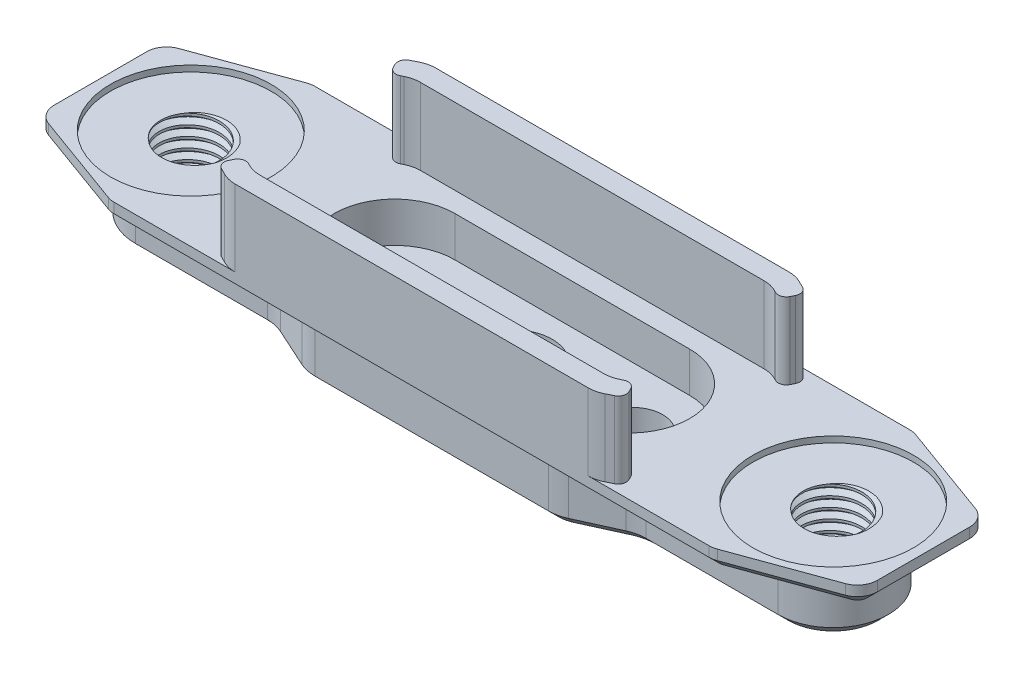
SolidWorks part; units mm, degrees
material "6061-T6 (SS)"
ref_plane "Front Plane" through (0, 0, 0) normal (0, 0, 1) x (1, 0, 0)
ref_plane "Top Plane" through (0, 0, 0) normal (0, 1, 0) x (1, 0, 0)
ref_plane "Right Plane" through (0, 0, 0) normal (1, 0, 0) x (0, 0, -1)
sketch "Sketch1" plane through (0, 0, 0) normal (0, 1, 0) x (1, 0, 0)
  line L1 (14.8238, -5) -> (-14.8238, -5)
  line L2 (20.5, -2.2996) -> (20.5, 2.2996)
  line L3 (14.8238, 5) -> (-14.8238, 5)
  line L4 (-20.5, -2.2996) -> (-20.5, 2.2996)
  line L5 (17.208, -4.1971) -> (-17.208, 4.1971) construction
  line L6 (17.208, 4.1971) -> (-17.208, -4.1971) construction
  line L9 (15.1656, 4.9398) -> (19.8417, 3.2394)
  line L11 (19.8417, -3.2394) -> (15.1656, -4.9398)
  line L12 (0, 7.9885) -> (0, -7.9189) construction
  line L13 (-19.8417, -3.2394) -> (-15.1656, -4.9398)
  line L14 (-15.1656, 4.9398) -> (-19.8417, 3.2394)
  arc A0 (-19.8417, 3.2394) -> (-20.5, 2.2996) centre (-19.5, 2.2996) ccw
  arc A1 (-19.8417, -3.2394) -> (-20.5, -2.2996) centre (-19.5, -2.2996) cw
  arc A2 (19.8417, -3.2394) -> (20.5, -2.2996) centre (19.5, -2.2996) ccw
  arc A3 (19.8417, 3.2394) -> (20.5, 2.2996) centre (19.5, 2.2996) cw
  arc A4 (-15.1656, 4.9398) -> (-14.8238, 5) centre (-14.8238, 4) cw
  arc A5 (-15.1656, -4.9398) -> (-14.8238, -5) centre (-14.8238, -4) ccw
  arc A6 (15.1656, -4.9398) -> (14.8238, -5) centre (14.8238, -4) cw
  arc A7 (15.1656, 4.9398) -> (14.8238, 5) centre (14.8238, 4) ccw
  point P0 (0, 0)
  point P8 (-20.5, 3)
  point P12 (-20.5, -3)
  point P24 (20.5, -3)
  point P27 (20.5, 3)
  point P30 (-15, 5)
  point P33 (-15, -5)
  point P36 (15, -5)
  point P39 (15, 5)
  dimension "D1" = 1
  dimension "D2" = 10
  dimension "D3" = 30
  dimension "D4" = 15
  dimension "D5" = 6
  dimension "D6" = 3
extrude "Boss-Extrude1" add sketch "Sketch1" along normal blind 1
chamfer "Chamfer1" distance 0.5 angle 45 16 edges at (0, 0, -5) (-14.9973, 0, -4.9848) (14.9973, 0, -4.9848) (-17.5037, 0, -4.0896) (17.5037, 0, -4.0896) (-20.3191, 0, -2.8733) (20.3191, 0, -2.8733) (-20.5, 0, 0) (20.5, 0, 0) (-20.3191, 0, 2.8733) (20.3191, 0, 2.8733) (-17.5037, 0, 4.0896) (17.5037, 0, 4.0896) (-14.9973, 0, 4.9848) (14.9973, 0, 4.9848) (0, 0, 5)
sketch "Sketch2" plane through (0, 0, 0) normal (0, -1, 0) x (1, 0, 0)
  line L0 (-16, 2.75) -> (-9.4332, 2.75)
  line L1 (5.8168, -4) -> (-5.8168, -4)
  line L3 (5.8168, 4) -> (-5.8168, 4)
  line L5 (9.4332, 2.75) -> (16, 2.75)
  line L7 (-16, -2.75) -> (-9.4332, -2.75)
  line L8 (-9, 0) -> (8.1313, 0) construction
  line L9 (6.6444, -3.8207) -> (8.6056, -2.9293)
  line L10 (-8.6056, -2.9293) -> (-6.6444, -3.8207)
  line L11 (-8.6056, 2.9293) -> (-6.6444, 3.8207)
  line L12 (9.4332, -2.75) -> (16, -2.75)
  line L13 (6.6444, 3.8207) -> (8.6056, 2.9293)
  arc A0 (8.6056, 2.9293) -> (9.4332, 2.75) centre (9.4332, 4.75) ccw
  arc A1 (6.6444, 3.8207) -> (5.8168, 4) centre (5.8168, 2) ccw
  arc A2 (-6.6444, 3.8207) -> (-5.8168, 4) centre (-5.8168, 2) cw
  arc A3 (-8.6056, 2.9293) -> (-9.4332, 2.75) centre (-9.4332, 4.75) cw
  arc A4 (-6.6444, -3.8207) -> (-5.8168, -4) centre (-5.8168, -2) ccw
  arc A5 (-8.6056, -2.9293) -> (-9.4332, -2.75) centre (-9.4332, -4.75) ccw
  arc A6 (8.6056, -2.9293) -> (9.4332, -2.75) centre (9.4332, -4.75) cw
  arc A7 (6.6444, -3.8207) -> (5.8168, -4) centre (5.8168, -2) cw
  circle A11 centre (0, 0) radius 2
  circle A12 centre (-6, 0) radius 1.5
  circle A13 centre (6, 0) radius 1.5
  arc A14 (-16, 2.75) -> (-16, -2.75) centre (-16, 0) ccw
  arc A15 (16, -2.75) -> (16, 2.75) centre (16, 0) ccw
  point P0 (0, 0)
  point P9 (-18.75, 0)
  point P16 (9, 2.75)
  point P23 (6.25, 4)
  point P26 (-6.25, 4)
  point P29 (-9, 2.75)
  point P32 (-6.25, -4)
  point P35 (-9, -2.75)
  point P38 (9, -2.75)
  point P41 (6.25, -4)
  point P50 (18.75, 0)
  dimension "D12" = 2
  dimension "D17" = 4
  dimension "D20" = 3
  dimension "D21" = 3
  dimension "D22" = 18.75
  dimension "D2" = 8
  dimension "D3" = 5.5
  dimension "D4" = 5.5
  dimension "D5" = 18
  dimension "D6" = 9
  dimension "D7" = 12.5
  dimension "D8" = 6.25
  dimension "D9" = 37.5
  dimension "D10" = 2.75
  dimension "D11" = 4
  dimension "D13" = 32
  dimension "D14" = 16
  dimension "D18" = 12
  dimension "D19" = 6
extrude "Boss-Extrude2" add sketch "Sketch2" along normal blind 3
chamfer "Chamfer2" distance 0.5 angle 45 20 edges at (12.7166, -3, 2.75) (9.0098, -3, 2.7953) (18.75, -3, 0) (7.625, -3, 3.375) (12.7166, -3, -2.75) (6.2402, -3, 3.9547) (9.0098, -3, -2.7953) (0, -3, 4) (7.625, -3, -3.375) (-6.2402, -3, 3.9547) (6.2402, -3, -3.9547) (-7.625, -3, 3.375) (0, -3, -4) (-9.0098, -3, 2.7953) (-6.2402, -3, -3.9547) (-12.7166, -3, 2.75) (-7.625, -3, -3.375) (-18.75, -3, 0) (-9.0098, -3, -2.7953) (-12.7166, -3, -2.75)
sketch "Sketch4" plane through (0, 1, 0) normal (0, 1, 0) x (1, 0, 0)
  circle A2 centre (-16, 0) radius 4
  circle A3 centre (16, 0) radius 4
  dimension "D1" = 32
  dimension "D2" = 16
  dimension "D3" = 8
  dimension "D4" = 8
extrude "Cut-Extrude2" cut sketch "Sketch4" against normal blind 0.3
sketch "Sketch5" plane through (0, 1, 0) normal (0, 1, 0) x (1, 0, 0)
  line L1 (5.85, -3) -> (-5.85, -3)
  line L3 (5.85, 3) -> (-5.85, 3)
  arc A0 (-5.85, 3) -> (-5.85, -3) centre (-5.85, 0) ccw
  arc A1 (5.85, -3) -> (5.85, 3) centre (5.85, 0) ccw
  point P0 (0, 0)
  point P1 (-8.85, 0)
  point P2 (8.85, 0)
  dimension "D3" = 8.85
  dimension "D1" = 17.7
  dimension "D2" = 6
extrude "Cut-Extrude3" cut sketch "Sketch5" against normal blind 2
sketch "Sketch6" plane through (0, 1, 0) normal (0, 1, 0) x (1, 0, 0)
  line L0 (-10.15, 7.0956) -> (-10.15, 1.2772) construction
  line L1 (-11.7314, 4.5) -> (12.299, 4.5) construction
  line L2 (10.15, 7.0956) -> (10.15, 2.7909) construction
  line L3 (14.8238, 5) -> (-14.8238, 5) construction
  line L4 (-9.15, 5.9263) -> (-9.15, 4.063) construction
  line L5 (-8.7959, 5) -> (8.7959, 5)
  line L6 (9.15, 5.9263) -> (9.15, 4.5569) construction
  line L7 (0, 0) -> (0, 2.7909) construction
  line L8 (-9.4667, 4.8416) -> (-9.7922, 4.6789)
  line L9 (9.4667, 4.8416) -> (9.7922, 4.6789)
  line L10 (9.2307, 3.8416) -> (9.345, 3.7845)
  line L11 (-8.5598, 4) -> (8.5598, 4)
  line L12 (-9.2307, 3.8416) -> (-9.345, 3.7845)
  line L13 (-9.9711, 4.1422) -> (-9.8817, 3.9633)
  line L14 (9.9711, 4.1422) -> (9.8817, 3.9633)
  line L15 (8.9139, 4) -> (9.7028, 3.6056) construction
  line L16 (-8.9139, 4) -> (8.9139, 4) construction
  line L17 (9.15, 5) -> (10.15, 4.5) construction
  line L18 (-9.15, 5) -> (9.15, 5) construction
  line L19 (-8.9139, 4) -> (-9.7028, 3.6056) construction
  line L20 (-9.15, 5) -> (-10.15, 4.5) construction
  line L21 (-6, 0) -> (6.1193, 0) construction
  line L22 (9.15, -5.9263) -> (9.15, -4.5569) construction
  line L23 (-9.15, -5.9263) -> (-9.15, -4.063) construction
  line L24 (-11.7314, -4.5) -> (12.299, -4.5) construction
  line L25 (9.9711, -4.1422) -> (9.8817, -3.9633)
  line L26 (-9.9711, -4.1422) -> (-9.8817, -3.9633)
  line L27 (-9.2307, -3.8416) -> (-9.345, -3.7845)
  line L28 (-8.5598, -4) -> (8.5598, -4)
  line L29 (9.2307, -3.8416) -> (9.345, -3.7845)
  line L30 (9.4667, -4.8416) -> (9.7922, -4.6789)
  line L31 (-9.4667, -4.8416) -> (-9.7922, -4.6789)
  line L32 (-8.7959, -5) -> (8.7959, -5)
  arc A1 (9.2307, 3.8416) -> (8.5598, 4) centre (8.5598, 2.5) ccw
  arc A2 (9.4667, 4.8416) -> (8.7959, 5) centre (8.7959, 3.5) ccw
  arc A4 (-8.5598, 4) -> (-9.2307, 3.8416) centre (-8.5598, 2.5) ccw
  arc A5 (-8.7959, 5) -> (-9.4667, 4.8416) centre (-8.7959, 3.5) ccw
  arc A6 (-9.8817, 3.9633) -> (-9.345, 3.7845) centre (-9.5239, 4.1422) ccw
  arc A7 (-9.9711, 4.1422) -> (-9.7922, 4.6789) centre (-9.6133, 4.3211) cw
  arc A8 (9.345, 3.7845) -> (9.8817, 3.9633) centre (9.5239, 4.1422) ccw
  arc A9 (9.9711, 4.1422) -> (9.7922, 4.6789) centre (9.6133, 4.3211) ccw
  arc A10 (9.9711, -4.1422) -> (9.7922, -4.6789) centre (9.6133, -4.3211) cw
  arc A11 (9.345, -3.7845) -> (9.8817, -3.9633) centre (9.5239, -4.1422) cw
  arc A12 (-9.9711, -4.1422) -> (-9.7922, -4.6789) centre (-9.6133, -4.3211) ccw
  arc A13 (-9.8817, -3.9633) -> (-9.345, -3.7845) centre (-9.5239, -4.1422) cw
  arc A14 (-8.7959, -5) -> (-9.4667, -4.8416) centre (-8.7959, -3.5) cw
  arc A15 (-8.5598, -4) -> (-9.2307, -3.8416) centre (-8.5598, -2.5) cw
  arc A16 (9.4667, -4.8416) -> (8.7959, -5) centre (8.7959, -3.5) cw
  arc A17 (9.2307, -3.8416) -> (8.5598, -4) centre (8.5598, -2.5) cw
  point P29 (9.15, 5)
  point P81 (9.15, -5)
  dimension "D6" = 1.5
  dimension "D7" = 0.4
  dimension "D1" = 20.3
  dimension "D2" = 10.15
  dimension "D3" = 0.5
  dimension "D4" = 1
  dimension "D5" = 9.15
extrude "Boss-Extrude3" add sketch "Sketch6" along normal blind 3.8
sketch "Sketch10" plane through (0, 0.7, 0) normal (0, 1, 0) x (1, 0, 0)
  circle A0 centre (-16, 0) radius 1.5
  circle A1 centre (16, 0) radius 1.5
  dimension "D1" = 3
  dimension "D2" = 3
extrude "Cut-Extrude4" cut sketch "Sketch10" against normal through all
thread "Thread4" pitch 0.5 method cut profile "Thread Profile5" start angle 0, offset 0, length 0, pitch 0.5, diameter 3
ref_plane "Plane5" through (-14.5, -3, 0) normal (0, 0, 1) x (1, 0, 0)
sketch "Thread Profile5" plane through (-14.5, -3, 0) normal (0, 0, 1) x (1, 0, 0)
  line L0 (0, 0) -> (0, 0.5) construction
  line L1 (0, 0) -> (0.2706, 0.1562)
  line L2 (0.2706, 0.1562) -> (0.2706, 0.2187)
  line L3 (0.2706, 0.2187) -> (0, 0.375)
  line L4 (0.2706, 0.1875) -> (0, 0.1875) construction
  line L11 (0, 0) -> (0, 0.375)
  point P2 (0, 0)
  dimension "Pitch" = 0.5
  dimension "Profile_Angle" = 60
  dimension "Profile_Land" = 0.0625
  dimension "Profile_Height" = 0.2706
thread "Thread5" pitch 0.5 method cut profile "Thread Profile6" start angle 0, offset 0, length 0, pitch 0.5, diameter 3
ref_plane "Plane6" through (17.5, -3, 0) normal (0, 0, 1) x (1, 0, 0)
sketch "Thread Profile6" plane through (17.5, -3, 0) normal (0, 0, 1) x (1, 0, 0)
  line L0 (0, 0) -> (0, 0.5) construction
  line L1 (0, 0) -> (0.2706, 0.1562)
  line L2 (0.2706, 0.1562) -> (0.2706, 0.2187)
  line L3 (0.2706, 0.2187) -> (0, 0.375)
  line L4 (0.2706, 0.1875) -> (0, 0.1875) construction
  line L11 (0, 0) -> (0, 0.375)
  point P2 (0, 0)
  dimension "Pitch" = 0.5
  dimension "Profile_Angle" = 60
  dimension "Profile_Land" = 0.0625
  dimension "Profile_Height" = 0.2706
